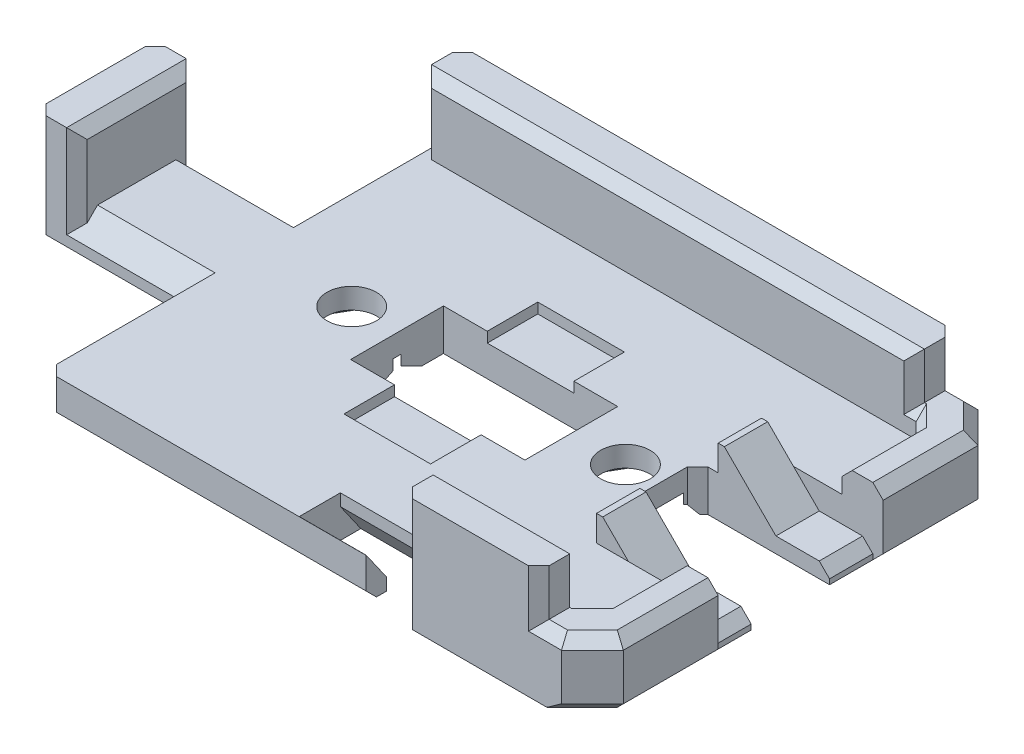
SolidWorks part; units mm, degrees
ref_plane "Front" through (0, 0, 0) normal (0, 0, 1) x (1, 0, 0)
ref_plane "Top" through (0, 0, 0) normal (0, 1, 0) x (1, 0, 0)
ref_plane "Right" through (0, 0, 0) normal (1, 0, 0) x (0, 0, -1)
sketch "Sketch1" plane through (0, 0, 0) normal (0, 1, 0) x (1, 0, 0)
  line L0 (0, 0) -> (-10910.2903, 0) construction
  line L1 (-33.6, -10.9132) -> (-33.6, 10.9132) construction
  line L2 (17.4, -8.229) -> (17.4, 8.229) construction
  line L3 (-25.7, -10.1) -> (-25.7, 10.1)
  line L4 (8.5, -10.1) -> (8.5, 10.1)
  line L5 (-25.7, 10.1) -> (8.5, 10.1)
  line L6 (-25.7, -10.1) -> (8.5, -10.1)
  line L11 (8.5, 4) -> (8, 4)
  line L12 (8, 4) -> (8, 1.9)
  line L13 (8, 1.9) -> (1.6, 1.9)
  line L14 (1.6, 1.9) -> (1.6, -1.9)
  line L15 (1.6, -1.9) -> (8, -1.9)
  line L16 (8, -1.9) -> (8, -4)
  line L17 (8, -4) -> (8.5, -4)
  line L18 (-6.85, 2.25) -> (-6.85, -2.25) construction
  line L19 (-18, -10.1) -> (-18, -2.9)
  line L20 (-18, -2.9) -> (-25.7, -2.9)
  line L21 (-6.85, 2.25) -> (-11.075, 2.25)
  line L22 (-18, 10.1) -> (-18, 2.9)
  line L23 (-18, 2.9) -> (-25.7, 2.9)
  line L24 (-11.075, 2.25) -> (-11.075, -2.25)
  line L25 (-11.075, -2.25) -> (-2.625, -2.25)
  line L26 (-2.625, -2.25) -> (-2.625, 2.25)
  line L27 (-2.625, 2.25) -> (-6.85, 2.25)
  circle A0 centre (-13.275, 0) radius 1.2
  circle A1 centre (0, 0) radius 1.2
  point P6 (-33.6, 0)
  point P9 (17.4, 0)
  point P16 (-25.7, 0)
  point P19 (8.5, 0)
  point P31 (1.6, 0)
  point P41 (-6.85, 0)
  dimension "D2" = 2.4
  dimension "D3" = 2.4
  dimension "D4" = 7.9
  dimension "D5" = 8.9
  dimension "D6" = 20.2
  dimension "D7" = 8.5
  dimension "D10" = 2.1
  dimension "D11" = 2.1
  dimension "D12" = 3.8
  dimension "D14" = 6.9
  dimension "D15" = 0.5
  dimension "D16" = 0.5
  dimension "D18" = 7.2
  dimension "D19" = 7.2
  dimension "D20" = 7.7
  dimension "D8" = 8.45
  dimension "D9" = 4.5
extrude "Boss-Extrude1" add sketch "Sketch1" along normal blind 2
sketch "Sketch2" plane through (0, 2, 0) normal (0, 1, 0) x (1, 0, 0)
  line L0 (-18, 10.1) -> (8.5, 10.1)
  line L1 (8.5, 10.1) -> (8.5, 4)
  line L2 (8.5, 4) -> (8, 4)
  line L3 (6.5, 4) -> (6.5, 8.1)
  line L4 (6.5, 8.1) -> (-18, 8.1)
  line L5 (-18, 8.1) -> (-18, 10.1)
  line L6 (-0.725, -8.1) -> (-0.725, -10.1)
  line L7 (8, 1.9) -> (1.6, 1.9) construction
  line L8 (2.6, 1.9) -> (8, 1.9)
  line L9 (2.6, 1.9) -> (2.6, 4)
  line L10 (2.6, 4) -> (6.5, 4)
  line L11 (8, 1.9) -> (8, 4)
  line L12 (8, 4) -> (6.5, 4) construction
  line L13 (6.5, 4) -> (8, 4) construction
  line L14 (-50, 0) -> (50, 0) construction
  line L15 (6.5, -4) -> (8, -4) construction
  line L16 (8, -4) -> (6.5, -4) construction
  line L17 (8, -1.9) -> (8, -4)
  line L18 (2.6, -4) -> (6.5, -4)
  line L19 (2.6, -1.9) -> (2.6, -4)
  line L20 (2.6, -1.9) -> (8, -1.9)
  line L22 (6.5, -8.1) -> (-0.725, -8.1)
  line L23 (6.5, -4) -> (6.5, -8.1)
  line L24 (8.5, -4) -> (8, -4)
  line L25 (8.5, -10.1) -> (8.5, -4)
  line L26 (-0.725, -10.1) -> (8.5, -10.1)
  line L27 (-6.85, -8.1) -> (-6.85, -10.1) construction
  line L28 (-18, -2.9) -> (-25.7, -2.9) construction
  line L29 (-25.7, 2.9) -> (-23.7, 2.9)
  line L30 (-25.7, 2.9) -> (-25.7, -2.9)
  line L31 (-25.7, -2.9) -> (-23.7, -2.9)
  line L32 (-23.7, 2.9) -> (-23.7, -2.9)
  line L33 (-18, 10.1) -> (-18, 2.9) construction
  line L35 (-0.725, -8.1) -> (-6.85, -8.1) construction
  line L36 (-6.85, -10.1) -> (-0.725, -10.1) construction
  dimension "D1" = 2
  dimension "D2" = 2
  dimension "D3" = 5.4
  dimension "D5" = 2
  dimension "D6" = 2
  dimension "D7" = 6.125
extrude "Boss-Extrude2" add sketch "Sketch2" along normal blind 1.25
sketch "Sketch3" plane through (0, 3.25, 0) normal (0, 1, 0) x (1, 0, 0)
  line L0 (5.9, 10.1) -> (5.9, 8.1)
  line L1 (8.5, 10.1) -> (-18, 10.1) construction
  line L2 (-18, 8.1) -> (6.5, 8.1) construction
  line L3 (5.9, 8.1) -> (-18, 8.1)
  line L4 (-18, 8.1) -> (-18, 10.1)
  line L5 (-18, 10.1) -> (5.9, 10.1)
  line L6 (8.5, 4) -> (8.5, 10.1) construction
  line L7 (-0.725, -8.1) -> (-0.725, -10.1)
  line L8 (-0.725, -10.1) -> (5.9, -10.1)
  line L9 (-18, 8.1) -> (6.5, 8.1) construction
  line L10 (5.9, -10.1) -> (5.9, -8.1)
  line L11 (6.5, -8.1) -> (-0.725, -8.1) construction
  line L12 (5.9, -8.1) -> (-0.725, -8.1)
  line L13 (-25.7, -2.9) -> (-23.7, -2.9)
  line L14 (-25.7, -2.9) -> (-25.7, 2.9)
  line L15 (-25.7, 2.9) -> (-23.7, 2.9)
  line L16 (-23.7, -2.9) -> (-23.7, 2.9)
  line L17 (6.5, -8.1) -> (-0.725, -8.1) construction
  line L19 (-0.725, -8.1) -> (-0.725, -10.1) construction
  line L20 (-0.725, -10.1) -> (8.5, -10.1) construction
  dimension "D1" = 2.6
extrude "Boss-Extrude3" add sketch "Sketch3" along normal blind 2.25
sketch "Sketch4" plane through (0, 0, 0) normal (0, 0, 1) x (1, 0, 0)
  line L0 (8.5, 0.75) -> (5.4, 0.75)
  line L1 (8.5, 3.25) -> (8.5, 0) construction
  line L2 (5.4, 0.75) -> (-0.6035, 6.7535)
  line L3 (-0.6035, 6.7535) -> (8.5, 6.7535)
  line L4 (8.5, 6.7535) -> (8.5, 0.75)
  line L5 (-18, 0) -> (8.5, 0) construction
  dimension "D1" = 3.1
  dimension "D2" = 45
  dimension "D3" = 0.75
extrude "Cut-Extrude1" cut sketch "Sketch4" against normal up to surface and the other way up to surface up to face at (8.25, 1.625, -4) other way up to face at (8.25, 1.625, 4)
sketch "Sketch5" plane through (0, 0, 0) normal (0, -1, 0) x (1, 0, 0)
  line L0 (0, 0) -> (-13.275, 0) construction
  line L1 (-15.5844, 0) -> (-14.4297, -2)
  line L2 (-14.4297, -2) -> (-12.1203, -2)
  line L3 (-12.1203, -2) -> (-10.9656, 0)
  line L4 (-10.9656, 0) -> (-12.1203, 2)
  line L5 (-12.1203, 2) -> (-14.4297, 2)
  line L6 (-14.4297, 2) -> (-15.5844, 0)
  line L7 (-2.3094, 0) -> (-1.1547, -2)
  line L8 (-1.1547, -2) -> (1.1547, -2)
  line L9 (1.1547, -2) -> (2.3094, 0)
  line L10 (2.3094, 0) -> (1.1547, 2)
  line L11 (1.1547, 2) -> (-1.1547, 2)
  line L12 (-1.1547, 2) -> (-2.3094, 0)
  circle A0 centre (-13.275, 0) radius 2 construction
  circle A1 centre (0, 0) radius 2 construction
  dimension "D1" = 4
  dimension "D2" = 4
extrude "Cut-Extrude2" cut sketch "Sketch5" against normal blind 1
sketch "Sketch6" plane through (0, 2, 0) normal (0, 1, 0) x (1, 0, 0)
  line L0 (-18, -10.1) -> (-0.725, -10.1) construction
  line L1 (-0.725, -8.1) -> (-5.725, -8.1)
  line L2 (-0.725, -8.1) -> (-0.725, -9.1)
  line L3 (-0.725, -9.1) -> (-5.725, -9.1)
  line L4 (-5.725, -8.1) -> (-5.725, -9.1)
  line L6 (-0.725, -9.1) -> (-2.475, -9.1)
  line L7 (-0.725, -9.1) -> (-0.725, -10.1)
  line L8 (-0.725, -10.1) -> (-2.475, -10.1)
  line L9 (-2.475, -9.1) -> (-2.475, -10.1)
  line M16 (-18, -10.1) -> (-0.725, -10.1)
  line M17 (-0.725, -10.1) -> (-0.725, -8.1)
  dimension "D1" = 1
  dimension "5" = 5
  dimension "2" = 1.75
extrude "Cut-Extrude3" cut sketch "Sketch6" against normal through all contours L3 L9 M16 M17 | L1 L4 L3 M17
chamfer "Chamfer5" distance 1.42 angle 35 2 edges at (-4.1, 2, 9.1) (-3.225, 0, 8.1)
chamfer "Chamfer2" distance 1.5 angle 45 2 edges at (8.5, 1.625, -10.1) (8.5, 1.625, 10.1)
chamfer "Chamfer4" distance 1 angle 45 2 edges at (-20.85, 2, 2.9) (-20.85, 2, -2.9)
chamfer "Chamfer1" distance 0.5 angle 45 44 edges at (6.5, 3.25, 6.05) (-23.7, 3.25, 2.9) (-23.7, 3.25, -2.9) (6.2, 3.25, -8.1) (5.9, 4.375, -10.1) (5.9, 4.375, -8.1) (-6.05, 5.5, -8.1) (6.45, 3.25, 10.1) (5.9, 4.375, 8.1) (5.9, 4.375, 10.1) (2.5875, 5.5, 8.1) (-23.7, 5.5, 0) (8, 0.75, 2.95) (8, 0.75, -2.95) (-5.5, 0, -10.1) (8.5, 0, -6.3) (8.25, 0, -4) (8.25, 0, 4) (-18, 0, 6.5) (-21.85, 0, 2.9) (-25.7, 0, 0) (8.5, 0, 6.3) (8.5, 3.25, 6.3) (-21.85, 0, -2.9) (7.75, 0, -9.35) (7.75, 0, 9.35) (7.75, 3.25, 9.35) (6.45, 3.25, -10.1) (-18, 0, -6.5) (7.75, 3.25, -9.35) (-18, 2.75, -10.1) (1.6, 1, -1.9) (1.6, 1, 1.9) (-18, 1, 10.1) (-25.7, 2.75, 2.9) (-25.7, 2.75, -2.9) (-18, 3.75, -8.1) (6.5, 2.625, -8.1) (6.5, 3.25, -6.05) (8.5, 3.25, -6.3) (6.5, 2.625, 8.1) (-0.725, 3.75, 8.1) (-0.725, 2.75, 10.1) (6.2, 3.25, 8.1)
chamfer "Chamfer3" distance 0.5 angle 45 12 edges at (-11.5976, 0, -1.0947) (-13.275, 0, -2) (-15.0071, 0, -1) (-15.0071, 0, 1) (-13.275, 0, 2) (-11.5976, 0, 1.0947) (1.3774, 0, -1.6144) (0, 0, -2) (-1.7321, 0, -1) (-1.7321, 0, 1) (0, 0, 2) (1.3774, 0, 1.6144)
sketch "Sketch7" plane through (0, 2, 0) normal (0, 1, 0) x (1, 0, 0)
  line L0 (-6.85, 2.25) -> (-6.85, -2.25) construction
  line L1 (-2.625, 2.25) -> (-11.075, 2.25) construction
  line L2 (-11.075, -2.25) -> (-2.625, -2.25) construction
  line L3 (-8.95, 4.7) -> (-8.95, -4.7)
  line L4 (-4.75, 4.7) -> (-4.75, -4.7)
  line L5 (-8.95, 4.7) -> (-4.75, 4.7)
  line L6 (-8.95, -4.7) -> (-4.75, -4.7)
  line L7 (-4.75, 0) -> (-8.95, 0) construction
  point P8 (-8.95, 0)
  point P14 (-6.85, 0)
  dimension "D1" = 2.1
  dimension "D2" = 2.1
  dimension "D3" = 9.4
extrude "Cut-Extrude4" cut sketch "Sketch7" against normal blind 0.5
equation "\"d\" = 51mm"
equation "\"D24@Sketch1\"=\"d\""
equation "\"phx\"= \"d\" - 11 - 15.5"
equation "\"middle\"= \"phx\" / 2"
equation "\"D21@Sketch1\"= \"middle\" + 3.1"
equation "\"D13@Sketch1\"= \"middle\" + \"middle\" / 2 + 3.4"
equation "\"D4@Sketch2\"=\"middle\"+ 3.1"
